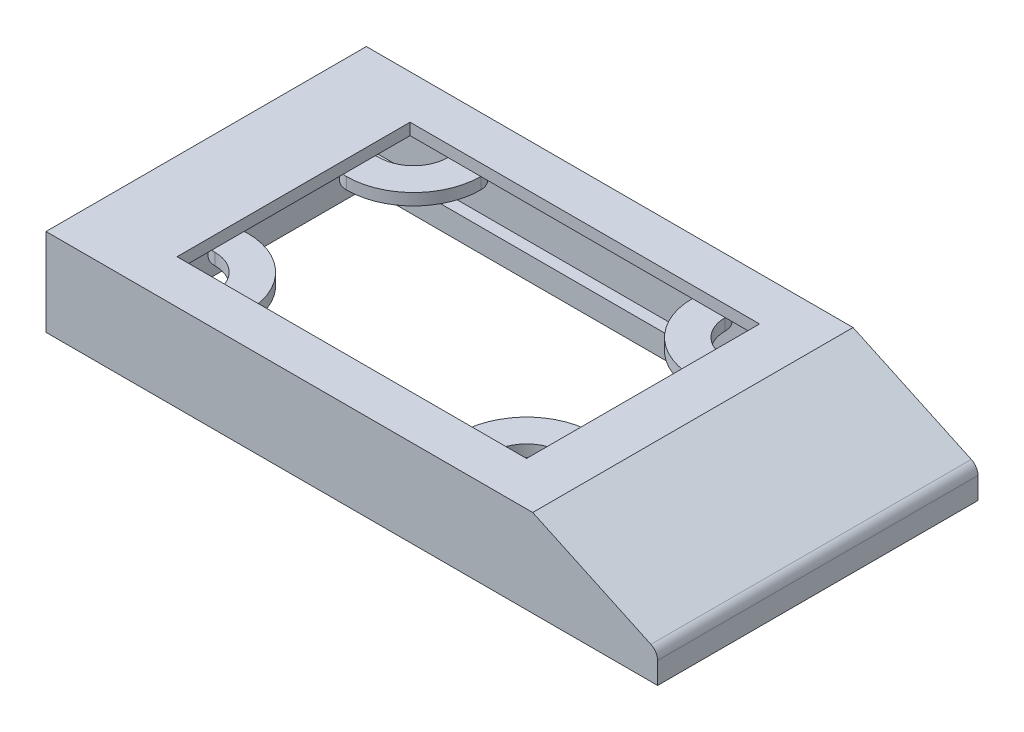
SolidWorks part; units mm, degrees
ref_plane "Ebene vorne" through (0, 0, 0) normal (0, 0, 1) x (1, 0, 0)
ref_plane "Ebene oben" through (0, 0, 0) normal (0, 1, 0) x (1, 0, 0)
ref_plane "Ebene rechts" through (0, 0, 0) normal (1, 0, 0) x (0, 0, -1)
sketch "Skizze1" plane through (0, 0, 0) normal (0, 1, 0) x (1, 0, 0)
  line L0 (0, 0) -> (105, 0)
  line L1 (-55, 0) -> (55, 0) construction
  line L2 (105, 0) -> (105, 55)
  line L3 (105, 55) -> (0, 55)
  line L4 (0, -55) -> (0, 55) construction
  line L5 (0, 55) -> (0, 0)
  dimension "D1" = 105
  dimension "D2" = 55
extrude "Aufsatz-Linear austragen1" add sketch "Skizze1" along normal blind 15
chamfer "Deckel_vorne" distance 10 angle 65 1 edges at (105, 15, -27.5) first distance on face at (105, 7.5, -27.5)
shell "Wandung1" thickness 2 removed face at (52.5, 0, -27.5)
fillet "Deckel_vorne_2" radius 2 1 edges at (105, 5, -27.5)
sketch "Skizze2" plane through (0, 15, 0) normal (0, 1, 0) x (1, 0, 0)
  line L0 (75, 7.5) -> (75, 47.5)
  line L1 (75, 47.5) -> (15, 47.5)
  line L2 (15, 47.5) -> (15, 7.5)
  line L3 (15, 7.5) -> (75, 7.5)
  line L6 (-8.25, 0) -> (8.25, 0) construction
  line L12 (0, -8.25) -> (0, 8.25) construction
  dimension "D1" = 60
  dimension "D2" = 40
  dimension "D3" = 15
  dimension "D4" = 7.5
extrude "Einsparung für Halterplatte" cut sketch "Skizze2" against normal up to surface (2 mm away) up to face at (42.5558, 13, -27.5)
ref_plane "Ebene_Magnet" through (0, 2, 0) normal (0, -1, 0) x (-1, 0, 0)
sketch "Skizze5" plane through (0, 2, 0) normal (0, -1, 0) x (-1, 0, 0)
  line L0 (-103, 53) -> (-2, 53) construction
  line L1 (-103, 2) -> (-103, 53) construction
  line L2 (-2, 2) -> (-103, 2) construction
  line L3 (-2, 53) -> (-2, 2) construction
  line L4 (-103, 53) -> (-2, 53)
  line L5 (-103, 2) -> (-103, 53)
  line L6 (-2, 2) -> (-103, 2)
  line L7 (-2, 53) -> (-2, 2)
  line L8 (-4, 51) -> (-4, 4)
  line L9 (-4, 4) -> (-101, 4)
  line L10 (-101, 4) -> (-101, 51)
  line L11 (-101, 51) -> (-4, 51)
  dimension "D1" = 2
extrude "Magnetaufsatz" add sketch "Skizze5" along normal blind 4
sketch "Skizze6" plane through (0, 13, 0) normal (0, -1, 0) x (1, 0, 0)
  line L0 (75, -47.5) -> (75, -7.5) construction
  line L1 (15, -47.5) -> (75, -47.5) construction
  line L2 (45.3021, -49.6047) -> (45.3021, -5.0029) construction
  line L3 (11.8722, -27.5) -> (77.0594, -27.5) construction
  arc A0 (75, -38.7795) -> (66.2795, -47.5) centre (75, -47.5) ccw construction
  arc A1 (75, -35.9592) -> (63.4592, -47.5) centre (75, -47.5) ccw
  arc A2 (75, -41.5997) -> (69.0997, -47.5) centre (75, -47.5) ccw
  arc A3 (75, -41.5997) -> (75, -35.9592) centre (75, -38.7795) ccw
  arc A4 (63.4592, -47.5) -> (69.0997, -47.5) centre (66.2795, -47.5) ccw
  arc A5 (15.6041, -38.7795) -> (24.3247, -47.5) centre (15.6041, -47.5) cw construction
  arc A10 (15.6041, -35.9592) -> (27.1449, -47.5) centre (15.6041, -47.5) cw
  arc A11 (15.6041, -41.5997) -> (21.5044, -47.5) centre (15.6041, -47.5) cw
  arc A12 (15.6041, -41.5997) -> (15.6041, -35.9592) centre (15.6041, -38.7795) cw
  arc A13 (27.1449, -47.5) -> (21.5044, -47.5) centre (24.3247, -47.5) cw
  arc A14 (15.6041, -16.2205) -> (24.3247, -7.5) centre (15.6041, -7.5) ccw construction
  arc A15 (15.6041, -19.0408) -> (27.1449, -7.5) centre (15.6041, -7.5) ccw
  arc A16 (15.6041, -13.4003) -> (21.5044, -7.5) centre (15.6041, -7.5) ccw
  arc A17 (15.6041, -13.4003) -> (15.6041, -19.0408) centre (15.6041, -16.2205) ccw
  arc A18 (27.1449, -7.5) -> (21.5044, -7.5) centre (24.3247, -7.5) ccw
  arc A19 (75, -16.2205) -> (66.2795, -7.5) centre (75, -7.5) cw construction
  arc A20 (75, -19.0408) -> (63.4592, -7.5) centre (75, -7.5) cw
  arc A21 (75, -13.4003) -> (69.0997, -7.5) centre (75, -7.5) cw
  arc A22 (75, -13.4003) -> (75, -19.0408) centre (75, -16.2205) cw
  arc A23 (63.4592, -7.5) -> (69.0997, -7.5) centre (66.2795, -7.5) cw
  point P8 (68.8336, -41.3336)
  point P20 (21.7705, -41.3336)
  point P25 (66.2795, -7.5)
  point P29 (21.7705, -13.6664)
  point P37 (68.8336, -13.6664)
extrude "Aufsatz-Linear austragen5" add sketch "Skizze6" along normal blind 2
